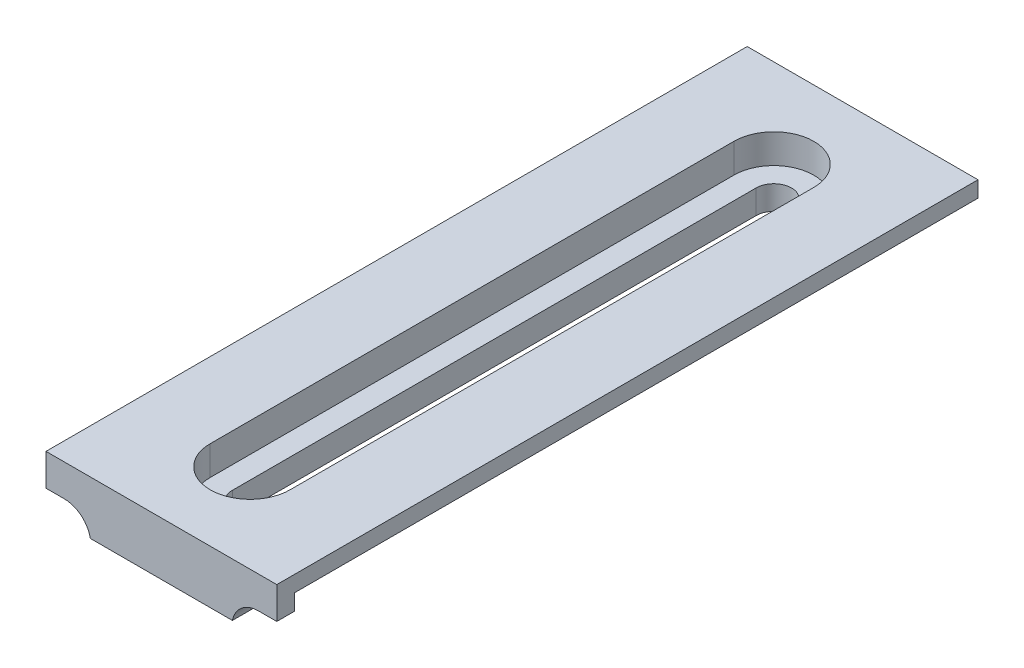
SolidWorks part; units mm, degrees
ref_plane "Płaszczyzna przednia" through (0, 0, 0) normal (0, 0, 1) x (1, 0, 0)
ref_plane "Płaszczyzna górna" through (0, 0, 0) normal (0, 1, 0) x (1, 0, 0)
ref_plane "Płaszczyzna prawa" through (0, 0, 0) normal (1, 0, 0) x (0, 0, -1)
sketch "Szkic1" plane through (0, 0, 0) normal (0, 0, 1) x (1, 0, 0)
  line L0 (-13, 0) -> (-13, 1.8)
  line L1 (-13, 1.8) -> (13, 1.8)
  line L2 (13, 1.8) -> (13, 0)
  line L3 (13, 0) -> (8, 0)
  line L4 (8, 0) -> (8, -4.2)
  line L5 (8, -4.2) -> (-8, -4.2)
  line L6 (-8, -4.2) -> (-8, 0)
  line L7 (-8, 0) -> (-13, 0)
  line L8 (0, 0) -> (0, 9.8508) construction
  point P11 (-10.5, 0)
  dimension "D1" = 26
  dimension "D2" = 16
  dimension "D3" = 6
  dimension "D4" = 1.8
extrude "Dodanie-wyciągnięcie1" add sketch "Szkic1" along normal blind 79
sketch "Szkic3" plane through (0, -4.2, 0) normal (0, -1, 0) x (1, 0, 0)
  line L0 (0, 69) -> (0, 10) construction
  line L1 (2, 69) -> (2, 10)
  line L2 (-2, 69) -> (-2, 10)
  line L3 (-8, 79) -> (8, 79) construction
  line L4 (-8, 0) -> (8, 0) construction
  arc A0 (2, 69) -> (-2, 69) centre (0, 69) ccw
  arc A1 (-2, 10) -> (2, 10) centre (0, 10) ccw
  point P3 (0, 39.5)
  point P8 (0, 71)
  dimension "D2" = 10
  dimension "D3" = 10
  dimension "D1" = 2
extrude "Wytnij-wyciągnięcie1" cut sketch "Szkic3" against normal through all
sketch "Szkic4" plane through (0, 1.8, 0) normal (0, 1, 0) x (1, 0, 0)
  line L0 (0, -69) -> (0, -10) construction
  line L1 (-4.5, -69) -> (-4.5, -10)
  line L2 (4.5, -69) -> (4.5, -10)
  arc A0 (-4.5, -69) -> (4.5, -69) centre (0, -69) ccw
  arc A1 (4.5, -10) -> (-4.5, -10) centre (0, -10) ccw
  point P4 (0, -39.5)
  dimension "D1" = 9
extrude "Wytnij-wyciągnięcie2" cut sketch "Szkic4" against normal blind 3.3
sketch "Szkic5" plane through (0, 0, 79) normal (0, 0, 1) x (1, 0, 0)
  line L1 (13, -1.8) -> (-13, -1.8)
  line L2 (13, -1.8) -> (13, 1.8)
  line L3 (13, 1.8) -> (-13, 1.8)
  line L4 (-13, -1.8) -> (-13, 1.8)
  line L5 (13, -1.8) -> (-13, 1.8) construction
  line L6 (13, 1.8) -> (-13, -1.8) construction
  point P0 (0, 0)
extrude "sdf" add sketch "Szkic5" against normal blind 2
fillet "Zaokrąglenie3" radius 3 2 edges at (8, -1.8, 78) (-8, -1.8, 78)
